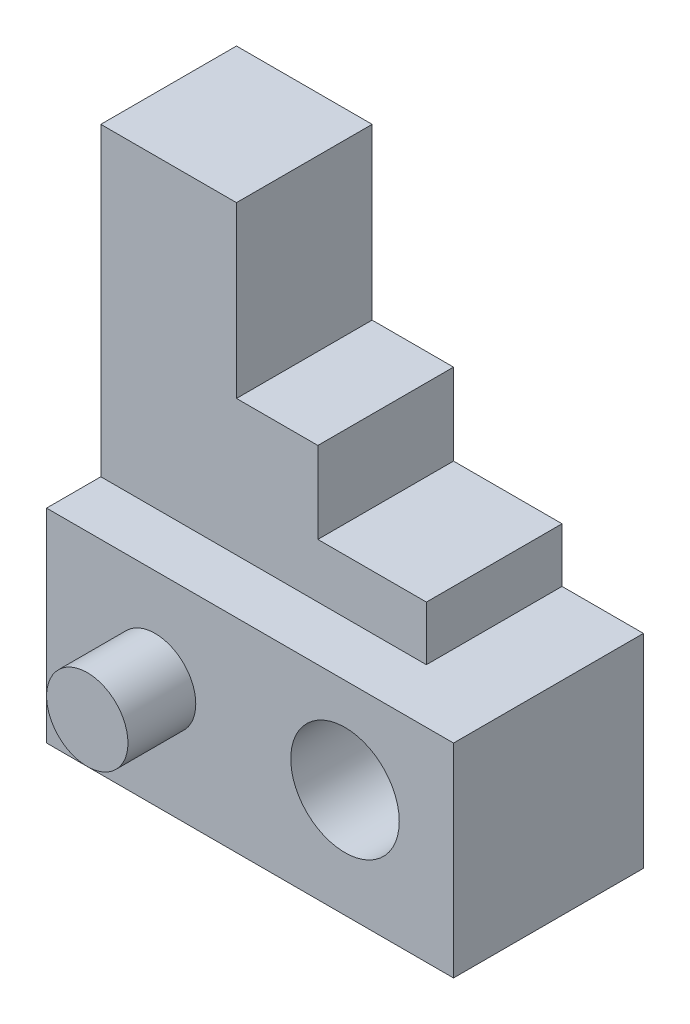
SolidWorks part; units mm, degrees
material "Aluminum Bronze"
ref_plane "Front Plane" through (0, 0, 0) normal (0, 0, 1) x (1, 0, 0)
ref_plane "Top Plane" through (0, 0, 0) normal (0, 1, 0) x (1, 0, 0)
ref_plane "Right Plane" through (0, 0, 0) normal (1, 0, 0) x (0, 0, -1)
sketch "Sketch1" plane through (0, 0, 0) normal (0, 0, 1) x (1, 0, 0)
  line L1 (0, 0) -> (60, 0)
  line L2 (0, 0) -> (0, 30)
  line L3 (0, 30) -> (60, 30)
  line L4 (60, 0) -> (60, 30)
  circle A0 centre (44, 16) radius 8
  dimension "D3" = 16
  dimension "D1" = 60
  dimension "D2" = 30
  dimension "D4" = 16
  dimension "D5" = 16
extrude "Boss-Extrude1" add sketch "Sketch1" along normal blind 28
sketch "Sketch2" plane through (0, 0, 0) normal (0, 0, 1) x (1, 0, 0)
  line L0 (0, 30) -> (0, 75)
  line L1 (0, 75) -> (20, 75)
  line L2 (20, 75) -> (20, 50)
  line L3 (20, 50) -> (32, 50)
  line L4 (32, 50) -> (32, 38)
  line L5 (32, 38) -> (48, 38)
  line L6 (48, 38) -> (48, 30)
  line L7 (60, 30) -> (0, 30) construction
  line L8 (48, 30) -> (0, 30)
  line L9 (0, 0) -> (60, 0) construction
  line L10 (60, 0) -> (60, 30) construction
  dimension "D1" = 75
  dimension "D2" = 12
  dimension "D3" = 12
  dimension "D4" = 12
  dimension "D5" = 20
  dimension "D6" = 20
extrude "Boss-Extrude2" add sketch "Sketch2" along normal blind 20
sketch "Sketch3" plane through (0, 0, 28) normal (0, 0, 1) x (1, 0, 0)
  line L0 (0, 0) -> (60, 0) construction
  line L1 (0, 0) -> (0, 30) construction
  circle A0 centre (16, 16) radius 6
  dimension "D3" = 12
  dimension "D1" = 16
  dimension "D2" = 16
extrude "Boss-Extrude3" add sketch "Sketch3" along normal blind 10 contours A0
